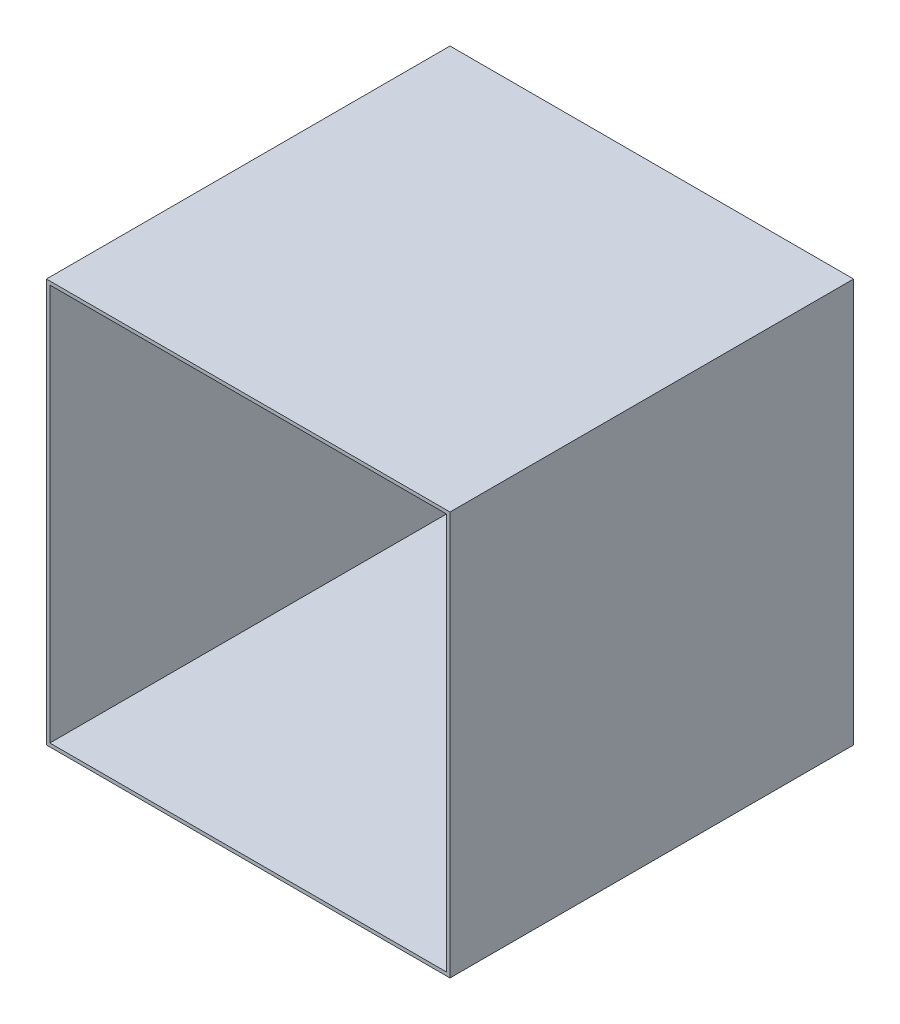
SolidWorks part; units mm, degrees
material "AISI 304"
ref_plane "Alzado" through (0, 0, 0) normal (0, 0, 1) x (1, 0, 0)
ref_plane "Planta" through (0, 0, 0) normal (0, 1, 0) x (1, 0, 0)
ref_plane "Vista lateral" through (0, 0, 0) normal (1, 0, 0) x (0, 0, -1)
sketch "Croquis1" plane through (0, 0, 0) normal (0, 0, 1) x (1, 0, 0)
  line L1 (0, 0) -> (70, 0)
  line L2 (0, 0) -> (0, 70)
  line L3 (0, 70) -> (70, 70)
  line L4 (70, 0) -> (70, 70)
  dimension "D1" = 70
  dimension "D2" = 70
extrude "Saliente-Extruir1" add sketch "Croquis1" along normal blind 70
shell "Vaciado1" thickness 0.6 removed face at (35, 35, 0) removed face at (35, 35, 70)
